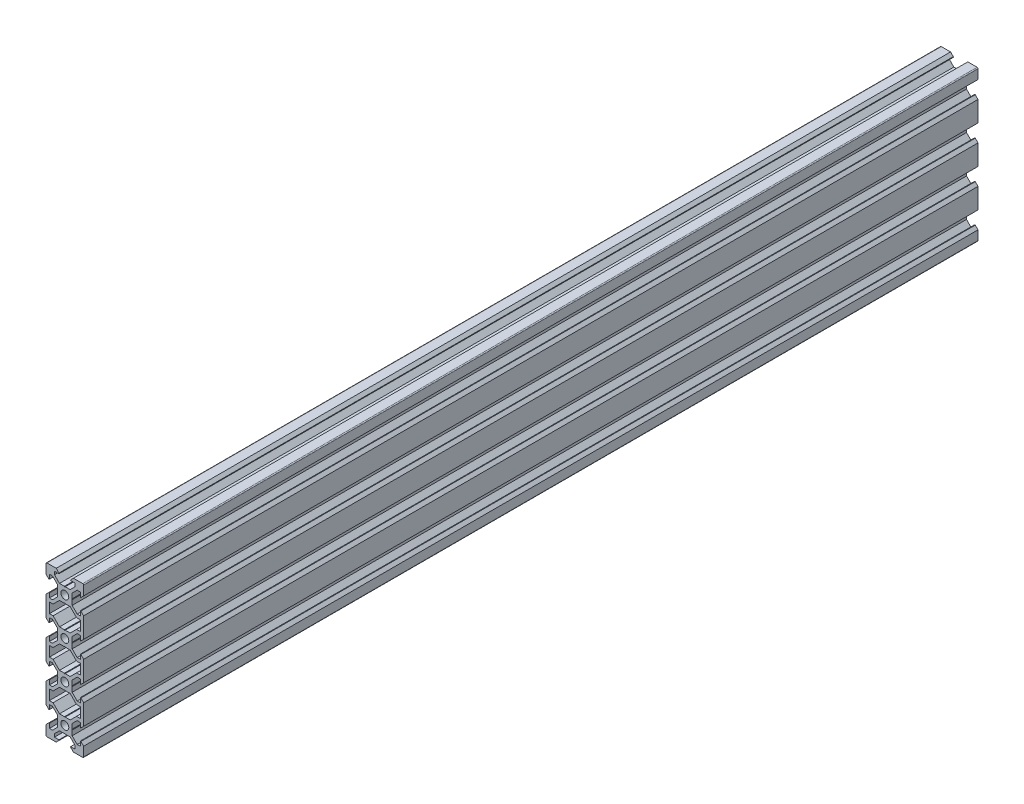
SolidWorks part; units mm, degrees
ref_plane "Plan de face" through (0, 0, 0) normal (0, 0, 1) x (1, 0, 0)
ref_plane "Plan de dessus" through (0, 0, 0) normal (0, 1, 0) x (1, 0, 0)
ref_plane "Plan de droite" through (0, 0, 0) normal (1, 0, 0) x (0, 0, -1)
ref_axis "Axe" through (0, 0, -13.782) along (0, 0, 1)
sketch "Esquisse1" plane through (0, 0, 0) normal (0, 0, 1) x (1, 0, 0)
  line L0 (0, 27.6392) -> (0, -27.6392) construction
  line L1 (-33.6074, 0) -> (33.6074, 0) construction
  line L2 (0, 0) -> (-22.2114, 22.2114) construction
  line L3 (-9.5, 10) -> (-4.58, 10)
  line L4 (-4.58, 10) -> (-3.125, 8.545)
  line L5 (-3.125, 8.545) -> (-3.125, 8.2)
  line L6 (-3.125, 8.2) -> (-5.5, 8.2)
  line L7 (-2.8393, 3.9) -> (-5.5, 6.5607)
  line L8 (-2.8393, 3.9) -> (-0.21, 3.9)
  line L9 (-5.5, 6.5607) -> (-5.5, 8.2)
  line L10 (0, 3.69) -> (0, 2.1)
  line L11 (-3.9, 2.8393) -> (-6.5607, 5.5)
  line L12 (-8.545, 3.125) -> (-8.2, 3.125)
  line L13 (-8.2, 3.125) -> (-8.2, 5.5)
  line L14 (-6.5607, 5.5) -> (-8.2, 5.5)
  line L15 (-10, 4.58) -> (-8.545, 3.125)
  line L16 (-10, 9.5) -> (-10, 4.58)
  line L17 (-0.21, 3.9) -> (0, 3.69)
  line L18 (-3.9, 2.8393) -> (-3.9, 0.21)
  line L19 (-6.2393, -12.7) -> (-8.2, -12.7)
  line L20 (-3.9, 0.21) -> (-3.69, 0)
  line L21 (-0.21, -3.9) -> (0, -3.69)
  line L22 (0, -3.69) -> (0, -2.1)
  line L23 (-6.5607, -5.5) -> (-8.2, -5.5)
  line L24 (-2.8393, -3.9) -> (-0.21, -3.9)
  line L25 (-8.545, -3.125) -> (-8.2, -3.125)
  line L26 (-10, -4.58) -> (-8.545, -3.125)
  line L27 (-8.2, -3.125) -> (-8.2, -5.5)
  line L28 (-2.8393, -3.9) -> (-6.2393, -7.3)
  line L29 (-3.9, -2.8393) -> (-6.5607, -5.5)
  line L30 (-3.9, -2.8393) -> (-3.9, -0.21)
  line L31 (-3.9, -0.21) -> (-3.69, 0)
  line L32 (-6.2393, -7.3) -> (-8.2, -7.3)
  line L33 (-8.2, -7.3) -> (-8.2, -12.7)
  line L34 (-8.2, -10) -> (-10, -10) construction
  line L35 (-10, -15.42) -> (-10, -4.58)
  line L36 (-3.9, -19.79) -> (-3.69, -20)
  line L37 (-3.9, -17.1607) -> (-3.9, -19.79)
  line L38 (-3.9, -17.1607) -> (-6.5607, -14.5)
  line L39 (-2.8393, -16.1) -> (-6.2393, -12.7)
  line L40 (-8.2, -16.875) -> (-8.2, -14.5)
  line L41 (-10, -15.42) -> (-8.545, -16.875)
  line L42 (-8.545, -16.875) -> (-8.2, -16.875)
  line L43 (-2.8393, -16.1) -> (-0.21, -16.1)
  line L44 (-6.5607, -14.5) -> (-8.2, -14.5)
  line L45 (0, -16.31) -> (0, -17.9)
  line L46 (-0.21, -16.1) -> (0, -16.31)
  line L47 (-8.2, -30) -> (-10, -30) construction
  line L48 (-3.69, -20) -> (0, -20) construction
  line L49 (-0.21, -23.9) -> (0, -23.69)
  line L50 (0, -23.69) -> (0, -22.1)
  line L51 (-6.5607, -25.5) -> (-8.2, -25.5)
  line L52 (-2.8393, -23.9) -> (-0.21, -23.9)
  line L53 (-8.545, -23.125) -> (-8.2, -23.125)
  line L54 (-10, -24.58) -> (-8.545, -23.125)
  line L55 (-8.2, -23.125) -> (-8.2, -25.5)
  line L56 (-2.8393, -23.9) -> (-6.2393, -27.3)
  line L57 (-3.9, -22.8393) -> (-6.5607, -25.5)
  line L58 (-3.9, -22.8393) -> (-3.9, -20.21)
  line L59 (-3.9, -20.21) -> (-3.69, -20)
  line L60 (-10, -24.58) -> (-10, -35.42)
  line L61 (-8.2, -32.7) -> (-8.2, -27.3)
  line L62 (-3.69, -40) -> (0, -40) construction
  line L63 (-8.2, -50) -> (-10, -50) construction
  line L64 (0, -60) -> (-22.2114, -82.2114) construction
  line L65 (-33.6074, -60) -> (33.6074, -60) construction
  line L66 (0, -87.6392) -> (0, -32.3608) construction
  line L67 (-6.2393, -32.7) -> (-8.2, -32.7)
  line L68 (-3.9, -39.79) -> (-3.69, -40)
  line L69 (-3.9, -37.1607) -> (-3.9, -39.79)
  line L70 (-3.9, -37.1607) -> (-6.5607, -34.5)
  line L71 (-2.8393, -36.1) -> (-6.2393, -32.7)
  line L72 (-8.2, -36.875) -> (-8.2, -34.5)
  line L73 (-10, -35.42) -> (-8.545, -36.875)
  line L74 (-8.545, -36.875) -> (-8.2, -36.875)
  line L75 (-6.2393, -27.3) -> (-8.2, -27.3)
  line L76 (-2.8393, -36.1) -> (-0.21, -36.1)
  line L77 (-6.5607, -34.5) -> (-8.2, -34.5)
  line L78 (0, -36.31) -> (0, -37.9)
  line L79 (-0.21, -36.1) -> (0, -36.31)
  line L80 (-0.21, -43.9) -> (0, -43.69)
  line L81 (0, -43.69) -> (0, -42.1)
  line L82 (-6.5607, -45.5) -> (-8.2, -45.5)
  line L83 (-2.8393, -43.9) -> (-0.21, -43.9)
  line L84 (-8.545, -43.125) -> (-8.2, -43.125)
  line L85 (-10, -44.58) -> (-8.545, -43.125)
  line L86 (-8.2, -43.125) -> (-8.2, -45.5)
  line L87 (-2.8393, -43.9) -> (-6.2393, -47.3)
  line L88 (-3.9, -42.8393) -> (-6.5607, -45.5)
  line L89 (-3.9, -42.8393) -> (-3.9, -40.21)
  line L90 (-3.9, -40.21) -> (-3.69, -40)
  line L91 (-10, -44.58) -> (-10, -55.42)
  line L92 (-8.2, -52.7) -> (-8.2, -47.3)
  line L93 (-6.2393, -52.7) -> (-8.2, -52.7)
  line L94 (-3.9, -59.79) -> (-3.69, -60)
  line L95 (-3.9, -57.1607) -> (-3.9, -59.79)
  line L96 (-3.9, -57.1607) -> (-6.5607, -54.5)
  line L97 (-2.8393, -56.1) -> (-6.2393, -52.7)
  line L98 (-8.2, -56.875) -> (-8.2, -54.5)
  line L99 (-10, -55.42) -> (-8.545, -56.875)
  line L100 (-8.545, -56.875) -> (-8.2, -56.875)
  line L101 (-2.8393, -56.1) -> (-0.21, -56.1)
  line L102 (-6.5607, -54.5) -> (-8.2, -54.5)
  line L103 (0, -56.31) -> (0, -57.9)
  line L104 (-0.21, -56.1) -> (0, -56.31)
  line L105 (-3.9, -60.21) -> (-3.69, -60)
  line L106 (-6.2393, -47.3) -> (-8.2, -47.3)
  line L107 (-3.9, -62.8393) -> (-3.9, -60.21)
  line L108 (-0.21, -63.9) -> (0, -63.69)
  line L109 (-10, -69.5) -> (-10, -64.58)
  line L110 (-10, -64.58) -> (-8.545, -63.125)
  line L111 (-6.5607, -65.5) -> (-8.2, -65.5)
  line L112 (-8.2, -63.125) -> (-8.2, -65.5)
  line L113 (-8.545, -63.125) -> (-8.2, -63.125)
  line L114 (-3.9, -62.8393) -> (-6.5607, -65.5)
  line L115 (0, -63.69) -> (0, -62.1)
  line L116 (-5.5, -66.5607) -> (-5.5, -68.2)
  line L117 (-2.8393, -63.9) -> (-0.21, -63.9)
  line L118 (-2.8393, -63.9) -> (-5.5, -66.5607)
  line L119 (-3.125, -68.2) -> (-5.5, -68.2)
  line L120 (-3.125, -68.545) -> (-3.125, -68.2)
  line L121 (-4.58, -70) -> (-3.125, -68.545)
  line L122 (-9.5, -70) -> (-4.58, -70)
  arc A0 (0, -2.1) -> (0, 2.1) centre (0, 0) cw
  arc A1 (-9.5, 10) -> (-10, 9.5) centre (-9.5, 9.5) ccw
  arc A2 (0, -42.1) -> (0, -37.9) centre (0, -40) cw
  arc A3 (-9.5, -70) -> (-10, -69.5) centre (-9.5, -69.5) cw
  arc A4 (0, -17.9) -> (0, -22.1) centre (0, -20) ccw
  arc A5 (0, -57.9) -> (0, -62.1) centre (0, -60) ccw
  point P4 (0, 0)
  point P7 (0, 0)
  point P30 (-10, 10)
  point P60 (0, -20)
  point P146 (-10, -70)
  dimension "D5" = 11
  dimension "D2" = 2.1
  dimension "D3" = 6.25
  dimension "D10" = 0.5
  dimension "D4" = 9.16
  dimension "D6" = 1.5
  dimension "D7" = 1.8
  dimension "D8" = 4.3
  dimension "D9" = 20
  dimension "D11" = 0.42
  dimension "D12" = 10
  dimension "D13" = 1.8
extrude "Boss.-Extru.1" add sketch "Esquisse1" along normal blind 475.2
sketch "Esquisse3" plane through (0, 0, 475.2) normal (0, 0, 1) x (1, 0, 0)
  line L0 (0, 0) -> (-9.8536, 9.8536) construction
  line L1 (-8.2, 8.2) -> (-8.2, 6.57)
  line L2 (-8.2, 6.57) -> (-7.54, 6.57)
  line L3 (-7.54, 6.57) -> (-6.57, 7.54)
  line L4 (-8.2, 3.125) -> (-8.2, 5.5) construction
  line L5 (-6.57, 8.2) -> (-6.57, 7.54)
  line L6 (-8.2, 8.2) -> (-6.57, 8.2)
  line L7 (-5.5, 6.5607) -> (-5.5, 8.2) construction
  line L8 (-10, -30) -> (6.918, -30) construction
  line L9 (-10, -24.58) -> (-10, -35.42) construction
  line L10 (-8.2, -68.2) -> (-6.57, -68.2)
  line L11 (-6.57, -68.2) -> (-6.57, -67.54)
  line L12 (-7.54, -66.57) -> (-6.57, -67.54)
  line L13 (-8.2, -66.57) -> (-7.54, -66.57)
  line L14 (-8.2, -68.2) -> (-8.2, -66.57)
  arc A0 (-9.5, 10) -> (-10, 9.5) centre (-9.5, 9.5) ccw construction
  point P13 (-7.055, 7.055)
  point P14 (-6.57, 7.87)
  point P26 (-7.055, -67.055)
  dimension "D1" = 1.07
extrude "Enlèv. mat.-Extru.1" [suppressed] cut sketch "Esquisse3" against normal through all
mirror "Symétrie1" about plane through (0, 3.69, 475.2) normal (-1, 0, 0) of "Enlèv. mat.-Extru.1", "Boss.-Extru.1"
